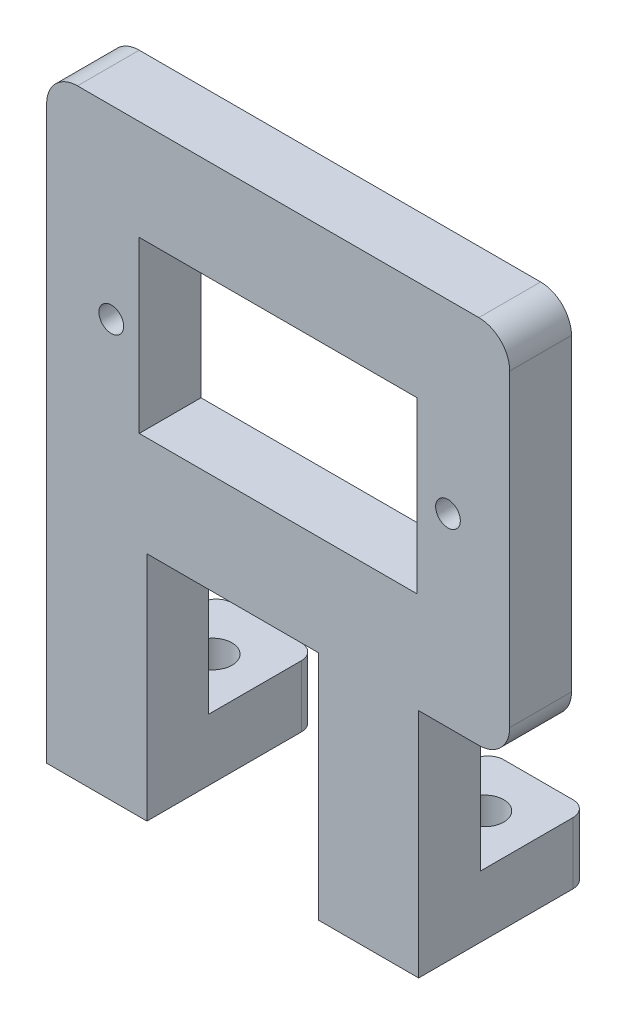
SolidWorks part; units mm, degrees
ref_plane "Front Plane" through (0, 0, 0) normal (0, 0, 1) x (1, 0, 0)
ref_plane "Top Plane" through (0, 0, 0) normal (0, 1, 0) x (1, 0, 0)
ref_plane "Right Plane" through (0, 0, 0) normal (1, 0, 0) x (0, 0, -1)
sketch "Sketch1" plane through (0, 0, 0) normal (0, 0, 1) x (1, 0, 0)
  line L0 (-19.05, -15.24) -> (-19.05, -34.29)
  line L1 (-11.43, 6.985) -> (11.43, 6.985)
  line L2 (-11.43, 6.985) -> (-11.43, -6.985)
  line L3 (-11.43, -6.985) -> (11.43, -6.985)
  line L4 (11.43, 6.985) -> (11.43, -6.985)
  line L5 (-19.05, 15.24) -> (19.05, 15.24)
  line L6 (-19.05, 15.24) -> (-19.05, -15.24)
  line L8 (19.05, 15.24) -> (19.05, -15.24)
  line L9 (-19.05, -34.29) -> (-10.795, -34.29)
  line L10 (-10.795, -34.29) -> (-10.795, -15.24)
  line L11 (-19.05, -15.24) -> (-10.795, -15.24)
  line L16 (3.302, -15.24) -> (3.302, -34.29)
  line L17 (3.302, -34.29) -> (11.557, -34.29)
  line L18 (11.557, -34.29) -> (11.557, -15.24)
  line L19 (11.557, -15.24) -> (3.302, -15.24)
  line L20 (19.05, -15.24) -> (-19.05, -15.24)
  line L21 (-19.05, -15.24) -> (-10.795, -15.24)
  line L22 (3.302, -15.24) -> (11.557, -15.24)
  point P5 (0, 6.985)
  point P6 (-11.43, 0)
  point P12 (0, 15.24)
  point P13 (-19.05, 0)
  dimension "D1" = 22.86
  dimension "D2" = 13.97
  dimension "D3" = 38.1
  dimension "D4" = 30.48
  dimension "D5" = 19.05
  dimension "D6" = 8.255
  dimension "D7" = 14.097
extrude "Boss-Extrude1" add sketch "Sketch1" along normal blind 5.08 contours L20 L8 L5 L6 | L11 L10 L9 L0 | L2 L1 L4 L3 | L19 L16 L17 L18
fillet "Fillet4" radius 2.54 3 edges at (19.05, 15.24, 2.54) (-19.05, 15.24, 2.54) (19.05, -15.24, 2.54)
ref_plane "Plane1" through (0, -34.29, 0) normal (0, 1, 0) x (1, 0, 0)
ref_plane "Plane2" through (-3.7465, 0, 0) normal (-1, 0, 0) x (0, 0, 1)
sketch "Sketch3" plane through (0, -34.29, 0) normal (0, 1, 0) x (1, 0, 0)
  line L0 (-19.05, 0) -> (-19.05, 8.89)
  line L1 (-19.05, 8.89) -> (-10.795, 8.89)
  line L2 (-10.795, 8.89) -> (-10.795, 0)
  line L3 (-16.51, 0) -> (16.51, 0) construction
  line L4 (-10.795, 0) -> (-19.05, 0)
  line L5 (-19.05, 0) -> (-10.795, 0) construction
  dimension "D2" = 8.89
extrude "Boss-Extrude2" add sketch "Sketch3" along normal blind 5.08
sketch "Sketch6" plane through (0, -29.21, 0) normal (0, 1, 0) x (1, 0, 0)
  line L0 (-19.05, 8.89) -> (-19.05, 0) construction
  line L1 (-10.795, 8.89) -> (-19.05, 8.89) construction
  circle A0 centre (-14.9225, 4.445) radius 1.6
  point P4 (-19.05, 4.445)
  point P7 (-14.9225, 8.89)
  dimension "D1" = 3.2
extrude "Cut-Extrude2" cut sketch "Sketch6" against normal blind 5.08
mirror "Mirror2" about plane through (-3.7465, 0, 0) normal (-1, 0, 0) of "Cut-Extrude2", "Boss-Extrude2"
fillet "Fillet3" radius 1.27 4 edges at (-10.795, -31.75, -8.89) (11.557, -31.75, -8.89) (3.302, -31.75, -8.89) (-19.05, -31.75, -8.89)
sketch "Sketch7" plane through (0, 0, 0) normal (0, 0, -1) x (-1, 0, 0)
  line L0 (-11.43, 6.985) -> (-11.43, -6.985) construction
  circle A0 centre (-13.97, 0) radius 1.016
  circle A1 centre (13.73, 0) radius 1.016
  dimension "D1" = 2.032
  dimension "D2" = 27.7
  dimension "D3" = 2.54
extrude "Cut-Extrude3" cut sketch "Sketch7" against normal through all
